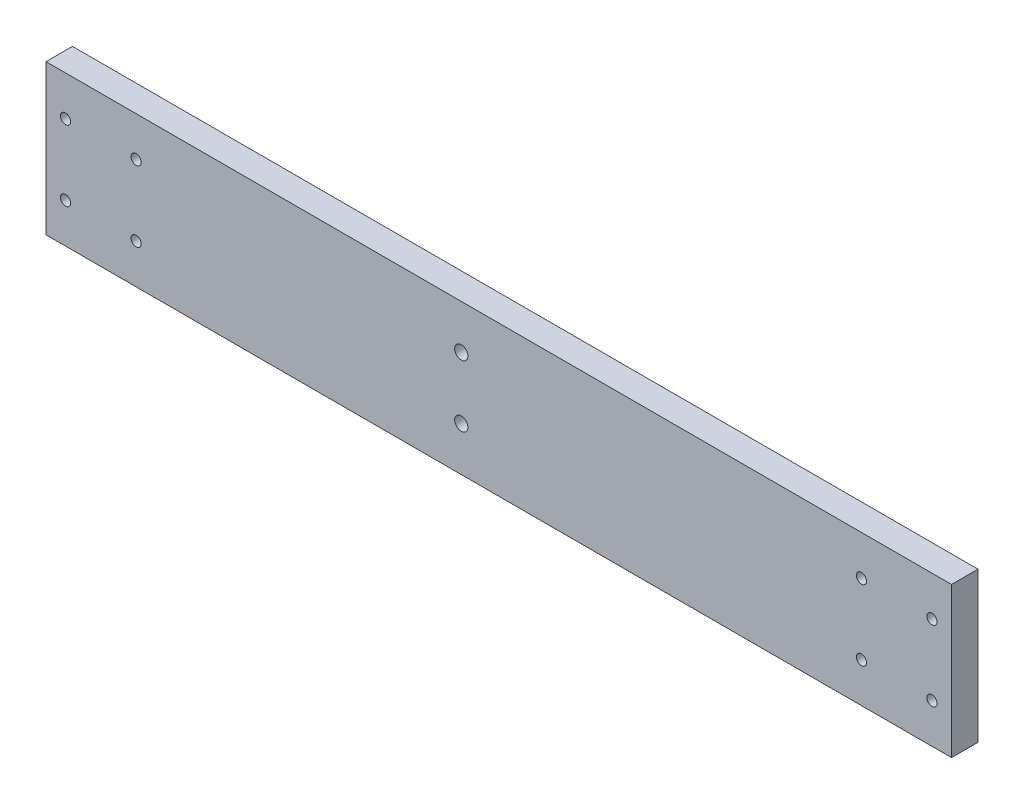
SolidWorks part; units mm, degrees
ref_plane "Plan de face" through (0, 0, 0) normal (0, 0, 1) x (1, 0, 0)
ref_plane "Plan de dessus" through (0, 0, 0) normal (0, 1, 0) x (1, 0, 0)
ref_plane "Plan de droite" through (0, 0, 0) normal (1, 0, 0) x (0, 0, -1)
sketch "Esquisse1" plane through (0, 0, 0) normal (0, 0, 1) x (1, 0, 0)
  line L1 (-102.63, 17) -> (102.63, 17)
  line L2 (-102.63, 17) -> (-102.63, -17)
  line L3 (-102.63, -17) -> (102.63, -17)
  line L4 (102.63, 17) -> (102.63, -17)
  dimension "D1" = 205.26
  dimension "D2" = 34
  dimension "D3" = 102.63
  dimension "D4" = 17
extrude "Boss.-Extru.1" add sketch "Esquisse1" along normal blind 6
sketch "Esquisse2" plane through (0, 0, 6) normal (0, 0, 1) x (1, 0, 0)
  line L0 (0, 49.0616) -> (0, -42.9956) construction
  line L1 (-102.63, 17) -> (-102.63, -17) construction
  line L2 (102.63, 17) -> (-102.63, 17) construction
  line L3 (-102.63, -17) -> (102.63, -17) construction
  circle A0 centre (-98.2, 8) radius 1.15
  circle A1 centre (-82.2, 8) radius 1.15
  circle A2 centre (-82.2, -8) radius 1.15
  circle A3 centre (-98.2, -8) radius 1.15
  circle A4 centre (98.2, -8) radius 1.15
  circle A5 centre (82.2, -8) radius 1.15
  circle A6 centre (82.2, 8) radius 1.15
  circle A7 centre (98.2, 8) radius 1.15
  circle A8 centre (-8.5, 7) radius 1.5
  circle A9 centre (-8.5, -7) radius 1.5
  dimension "D1" = 2.3
  dimension "D2" = 2.3
  dimension "D3" = 2.3
  dimension "D4" = 2.3
  dimension "D12" = 3
  dimension "D14" = 3
  dimension "D5" = 4.43
  dimension "D6" = 9
  dimension "D7" = 9
  dimension "D8" = 16
  dimension "D9" = 16
  dimension "D10" = 16
  dimension "D11" = 16
  dimension "D13" = 10
  dimension "D15" = 10
  dimension "D16" = 14
  dimension "D17" = 8.5
extrude "Enlèv. mat.-Extru.1" cut sketch "Esquisse2" against normal blind 6
